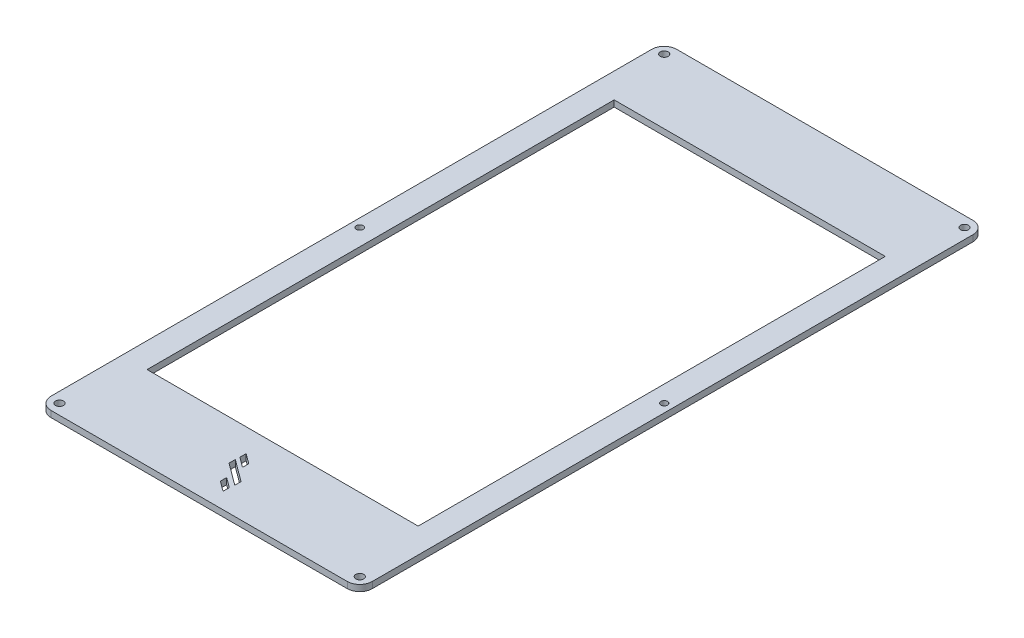
SolidWorks part; units mm, degrees
ref_plane "前视基准面" through (0, 0, 0) normal (0, 0, 1) x (1, 0, 0)
ref_plane "上视基准面" through (0, 0, 0) normal (0, 1, 0) x (1, 0, 0)
ref_plane "右视基准面" through (0, 0, 0) normal (1, 0, 0) x (0, 0, -1)
sketch "草图1" plane through (0.249, 0, -75.7072) normal (0, 1, 0) x (1, 0, 0)
  line L0 (-212.3169, 718.1207) -> (-234.7066, 815.582) construction
  line L1 (-132.5632, 1387.3532) -> (-132.5632, 1244.1403) construction
  line L2 (-45.1474, 1386.0064) -> (-45.1474, 1242.0064)
  line L3 (-110.6474, 1387.5064) -> (-86.8035, 1387.5064)
  line L4 (-120.6474, 1377.5064) -> (-120.6474, 1369.0064)
  line L5 (-110.6474, 1240.5064) -> (-86.8035, 1240.5064)
  line L6 (-46.6474, 1377.5064) -> (-46.6474, 1369.0064)
  line L7 (-119.1474, 1239.0064) -> (-48.1474, 1239.0064)
  line L8 (-122.1474, 1386.0064) -> (-122.1474, 1242.0064)
  line L9 (-119.1474, 1389.0064) -> (-48.1474, 1389.0064)
  line L10 (-120.6474, 1240.5064) -> (-46.6474, 1240.5064) construction
  line L11 (-46.6474, 1387.5064) -> (-46.6474, 1240.5064) construction
  line L12 (-120.6474, 1387.5064) -> (-120.6474, 1240.5064) construction
  line L13 (-120.6474, 1387.5064) -> (-46.6474, 1387.5064) construction
  line L14 (-45.1474, 1389.0064) -> (-45.1474, 1239.0064) construction
  line L15 (-122.1474, 1239.0064) -> (-45.1474, 1239.0064) construction
  line L16 (-122.1474, 1389.0064) -> (-122.1474, 1239.0064) construction
  line L17 (-122.1474, 1389.0064) -> (-45.1474, 1389.0064) construction
  line L18 (-83.6474, 1387.5064) -> (-83.6474, 1240.5064) construction
  line L19 (-46.6474, 1369.0064) -> (-49.0442, 1369.0064)
  line L21 (-46.6474, 1366.0064) -> (-49.0442, 1366.0064)
  line L22 (-49.0442, 1369.0064) -> (-49.0442, 1366.0064)
  line L23 (-46.6474, 1314.0064) -> (-120.6474, 1314.0064) construction
  line L24 (-46.6474, 1366.0064) -> (-46.6474, 1262.0064)
  line L25 (-46.6474, 1259.0064) -> (-49.0442, 1259.0064)
  line L26 (-49.0442, 1259.0064) -> (-49.0442, 1262.0064)
  line L27 (-46.6474, 1262.0064) -> (-49.0442, 1262.0064)
  line L28 (-120.6474, 1369.0064) -> (-118.2507, 1369.0064)
  line L29 (-118.2507, 1369.0064) -> (-118.2507, 1366.0064)
  line L30 (-120.6474, 1366.0064) -> (-118.2507, 1366.0064)
  line L31 (-120.6474, 1262.0064) -> (-118.2507, 1262.0064)
  line L32 (-118.2507, 1259.0064) -> (-118.2507, 1262.0064)
  line L33 (-46.6474, 1259.0064) -> (-46.6474, 1250.5064)
  line L34 (-120.6474, 1366.0064) -> (-120.6474, 1262.0064)
  line L35 (-118.2507, 1259.0064) -> (-120.6474, 1259.0064)
  line L36 (-120.6474, 1259.0064) -> (-120.6474, 1250.5064)
  line L37 (-79.37, 1387.5064) -> (-56.6474, 1387.5064)
  line L39 (-79.37, 1387.5064) -> (-79.37, 1384.5064)
  line L40 (-79.37, 1384.5064) -> (-86.8035, 1384.5064)
  line L41 (-86.8035, 1387.5064) -> (-86.8035, 1384.5064)
  line L43 (-80.7882, 1240.5064) -> (-80.7882, 1243.5064)
  line L44 (-80.7882, 1243.5064) -> (-86.8035, 1243.5064)
  line L45 (-86.8035, 1240.5064) -> (-86.8035, 1243.5064)
  line L46 (-80.7882, 1240.5064) -> (-56.6474, 1240.5064)
  arc A0 (-56.6474, 1240.5064) -> (-46.6474, 1250.5064) centre (-56.6474, 1250.5064) ccw
  arc A1 (-120.6474, 1250.5064) -> (-110.6474, 1240.5064) centre (-110.6474, 1250.5064) ccw
  arc A2 (-110.6474, 1387.5064) -> (-120.6474, 1377.5064) centre (-110.6474, 1377.5064) ccw
  arc A3 (-56.6474, 1387.5064) -> (-46.6474, 1377.5064) centre (-56.6474, 1377.5064) cw
  arc A4 (-45.1474, 1242.0064) -> (-48.1474, 1239.0064) centre (-48.1474, 1242.0064) cw
  arc A5 (-119.1474, 1239.0064) -> (-122.1474, 1242.0064) centre (-119.1474, 1242.0064) cw
  arc A6 (-122.1474, 1386.0064) -> (-119.1474, 1389.0064) centre (-119.1474, 1386.0064) cw
  arc A7 (-45.1474, 1386.0064) -> (-48.1474, 1389.0064) centre (-48.1474, 1386.0064) ccw
  point P48 (-47.8458, 1259.0064)
  point P55 (-119.4491, 1259.0064)
  dimension "D3" = 10
  dimension "D4" = 3
  dimension "D1" = 100
  dimension "D5" = 3
  dimension "D6" = 20
  dimension "D7" = 2.3967
  dimension "D8" = 71
  dimension "D9" = 144
  dimension "D10" = 3
  dimension "D11" = 3
  dimension "D2" = 1.5
extrude "凸台-拉伸1" add sketch "草图1" along normal blind 15
fillet "圆角1" radius 1 12 edges at (-118.0016, 7.5, -1334.7135) (-118.0016, 7.5, -1337.7135) (-48.7951, 7.5, -1334.7135) (-48.7951, 7.5, -1337.7135) (-48.7951, 7.5, -1441.7135) (-48.7951, 7.5, -1444.7135) (-118.0016, 7.5, -1441.7135) (-118.0016, 7.5, -1444.7135) (-86.5544, 7.5, -1319.2135) (-80.5392, 7.5, -1319.2135) (-79.1209, 7.5, -1460.2135) (-86.5544, 7.5, -1460.2135)
sketch "草图2" plane through (0.249, 15, -75.7072) normal (0, 1, 0) x (1, 0, 0)
  line L0 (-117.9843, 1353.593) -> (-118.8671, 1253.5969) construction
  line L1 (-65.1474, 1308.7566) -> (-65.1474, 1318.5064)
  line L2 (-66.1474, 1319.5064) -> (-92.1474, 1319.5064)
  line L3 (-93.1474, 1318.5064) -> (-93.1474, 1313.0064)
  line L4 (-45.1474, 1242.0064) -> (-45.1474, 1386.0064)
  line L5 (-48.1474, 1389.0064) -> (-119.1474, 1389.0064)
  line L6 (-122.1474, 1386.0064) -> (-122.1474, 1242.0064)
  line L7 (-119.1474, 1239.0064) -> (-48.1474, 1239.0064)
  line L8 (-45.1474, 1242.0064) -> (-45.1474, 1386.0064)
  line L9 (-48.1474, 1389.0064) -> (-119.1474, 1389.0064)
  line L10 (-122.1474, 1386.0064) -> (-122.1474, 1242.0064)
  line L11 (-119.1474, 1239.0064) -> (-48.1474, 1239.0064)
  line L12 (-94.1474, 1312.0064) -> (-95.1474, 1312.0064)
  line L13 (-96.1474, 1311.0064) -> (-96.1474, 1305.0064)
  line L14 (-95.1474, 1304.0064) -> (-86.1474, 1304.0064)
  line L15 (-85.1474, 1303.0064) -> (-85.1474, 1274.0064)
  line L16 (-84.1474, 1273.0064) -> (-65.1474, 1273.0064)
  line L17 (-89.1474, 1277.5064) -> (-99.1474, 1277.5064)
  line L18 (-100.1474, 1278.5064) -> (-100.1474, 1283.5064)
  line L19 (-99.1474, 1284.5064) -> (-89.1474, 1284.5064)
  line L20 (-88.1474, 1283.5064) -> (-88.1474, 1278.5064)
  line L21 (-84.6474, 1378.5064) -> (-84.6474, 1328.5064) construction
  line L22 (-104.1474, 1374.0064) -> (-65.1474, 1374.0064)
  line L23 (-105.1474, 1373.0064) -> (-105.1474, 1334.0064)
  line L24 (-104.1474, 1333.0064) -> (-65.1474, 1333.0064)
  line L25 (-64.1474, 1373.0064) -> (-64.1474, 1334.0064)
  line L26 (-65.1474, 1273.0064) -> (-64.1474, 1273.0064)
  line L27 (-65.1474, 1308.7566) -> (-55.8177, 1308.7566)
  line L28 (-64.1474, 1273.0064) -> (-64.1474, 1269.7566)
  line L29 (-63.1474, 1268.7566) -> (-56.8177, 1268.7566)
  line L30 (-55.8177, 1308.7566) -> (-55.8177, 1269.7566)
  arc A0 (-65.1474, 1318.5064) -> (-66.1474, 1319.5064) centre (-66.1474, 1318.5064) ccw
  arc A2 (-85.1474, 1274.0064) -> (-84.1474, 1273.0064) centre (-84.1474, 1274.0064) ccw
  arc A3 (-86.1474, 1304.0064) -> (-85.1474, 1303.0064) centre (-86.1474, 1303.0064) cw
  arc A4 (-48.1474, 1239.0064) -> (-45.1474, 1242.0064) centre (-48.1474, 1242.0064) ccw
  arc A5 (-45.1474, 1386.0064) -> (-48.1474, 1389.0064) centre (-48.1474, 1386.0064) ccw
  arc A6 (-119.1474, 1389.0064) -> (-122.1474, 1386.0064) centre (-119.1474, 1386.0064) ccw
  arc A7 (-122.1474, 1242.0064) -> (-119.1474, 1239.0064) centre (-119.1474, 1242.0064) ccw
  arc A8 (-48.1474, 1239.0064) -> (-45.1474, 1242.0064) centre (-48.1474, 1242.0064) ccw
  arc A9 (-45.1474, 1386.0064) -> (-48.1474, 1389.0064) centre (-48.1474, 1386.0064) ccw
  arc A10 (-119.1474, 1389.0064) -> (-122.1474, 1386.0064) centre (-119.1474, 1386.0064) ccw
  arc A11 (-122.1474, 1242.0064) -> (-119.1474, 1239.0064) centre (-119.1474, 1242.0064) ccw
  arc A12 (-92.1474, 1319.5064) -> (-93.1474, 1318.5064) centre (-92.1474, 1318.5064) ccw
  arc A13 (-93.1474, 1313.0064) -> (-94.1474, 1312.0064) centre (-94.1474, 1313.0064) cw
  arc A14 (-95.1474, 1312.0064) -> (-96.1474, 1311.0064) centre (-95.1474, 1311.0064) ccw
  arc A15 (-96.1474, 1305.0064) -> (-95.1474, 1304.0064) centre (-95.1474, 1305.0064) ccw
  arc A16 (-89.1474, 1284.5064) -> (-88.1474, 1283.5064) centre (-89.1474, 1283.5064) cw
  arc A17 (-89.1474, 1277.5064) -> (-88.1474, 1278.5064) centre (-89.1474, 1278.5064) ccw
  arc A18 (-99.1474, 1277.5064) -> (-100.1474, 1278.5064) centre (-99.1474, 1278.5064) cw
  arc A19 (-100.1474, 1283.5064) -> (-99.1474, 1284.5064) centre (-99.1474, 1283.5064) cw
  arc A20 (-65.1474, 1333.0064) -> (-64.1474, 1334.0064) centre (-65.1474, 1334.0064) ccw
  arc A21 (-105.1474, 1334.0064) -> (-104.1474, 1333.0064) centre (-104.1474, 1334.0064) ccw
  arc A22 (-104.1474, 1374.0064) -> (-105.1474, 1373.0064) centre (-104.1474, 1373.0064) ccw
  arc A23 (-65.1474, 1374.0064) -> (-64.1474, 1373.0064) centre (-65.1474, 1373.0064) cw
  circle A24 centre (-84.6474, 1378.5064) radius 1.5
  circle A25 centre (-84.6474, 1328.5064) radius 1.5
  arc A26 (-64.1474, 1269.7566) -> (-63.1474, 1268.7566) centre (-63.1474, 1269.7566) ccw
  arc A27 (-56.8177, 1268.7566) -> (-55.8177, 1269.7566) centre (-56.8177, 1269.7566) ccw
  point P28 (-65.1474, 1319.5064)
  point P31 (-65.1474, 1273.0064)
  point P34 (-85.1474, 1273.0064)
  point P37 (-85.1474, 1304.0064)
  point P40 (-93.1474, 1319.5064)
  point P43 (-93.1474, 1312.0064)
  point P46 (-96.1474, 1312.0064)
  point P49 (-96.1474, 1304.0064)
  point P52 (-88.1474, 1284.5064)
  point P55 (-88.1474, 1277.5064)
  point P58 (-100.1474, 1277.5064)
  point P69 (-105.1474, 1333.0064)
  point P72 (-105.1474, 1374.0064)
  point P75 (-64.1474, 1374.0064)
  point P78 (-84.6474, 1353.5064)
  point P79 (-64.1474, 1353.5064)
  dimension "D15" = 1
  dimension "D20" = 1
  dimension "D22" = 34
  dimension "D23" = 1
  dimension "D2" = 100
  dimension "D3" = 20
  dimension "D4" = 28
  dimension "D5" = 7.5
  dimension "D6" = 8
  dimension "D7" = 11
  dimension "D8" = 3
  dimension "D9" = 31
  dimension "D10" = 39
  dimension "D11" = 46.5
  dimension "D12" = 22
  dimension "D13" = 12
  dimension "D14" = 7
  dimension "D16" = 19
  dimension "D17" = 15
  dimension "D18" = 41
  dimension "D19" = 41
  dimension "D21" = 50
  dimension "D24" = 38.5
  dimension "D1" = 0
extrude "凸台-拉伸2" add sketch "草图2" against normal blind 2
fillet "圆角7" radius 1 3 edges at (-63.8984, 14, -1348.7135) (-55.5686, 14, -1384.4637) (-64.8984, 14, -1384.4637)
fillet "圆角2" radius 1 50 edges at (-78.8984, 15, -1395.2135) (-92.6055, 15, -1394.9206) (-92.8984, 15, -1391.4635) (-93.1913, 15, -1388.0064) (-94.3984, 15, -1387.7135) (-95.6055, 15, -1387.4206) (-95.8984, 15, -1383.7135) (-95.6055, 15, -1380.0064) (-90.3984, 15, -1379.7135) (-85.1913, 15, -1379.4206) (-84.8984, 15, -1364.2135) (-84.6055, 15, -1349.0064) (-74.3984, 15, -1348.7135) (-64.8984, 15, -1389.8386) (-65.1913, 15, -1394.9206) (-93.8984, 15, -1360.2135) (-99.6055, 15, -1359.9206) (-99.8984, 15, -1356.7135) (-99.6055, 15, -1353.5064) (-93.8984, 15, -1353.2135) (-88.1913, 15, -1353.5064) (-87.8984, 15, -1356.7135) (-88.1913, 15, -1359.9206) (-83.3984, 15, -1314.7135) (-121.0197, 15, -1315.5922) (-121.8984, 15, -1389.7135) (-121.0197, 15, -1463.8349) (-83.3984, 15, -1464.7135) (-45.7771, 15, -1463.8349) (-44.8984, 15, -1389.7135) (-45.7771, 15, -1315.5922) (-63.8984, 15, -1429.2135) (-64.1913, 15, -1449.4206) (-84.3984, 15, -1449.7135) (-104.6055, 15, -1449.4206) (-104.8984, 15, -1429.2135) (-104.6055, 15, -1409.0064) (-84.3984, 15, -1408.7135) (-64.1913, 15, -1409.0064) (-84.3984, 15, -1452.7135) (-84.3984, 15, -1402.7135) (-59.7335, 15, -1344.4637) (-55.8615, 15, -1344.7566) (-55.5686, 15, -1364.4637) (-60.2335, 15, -1384.4637) (-63.8984, 15, -1346.5886) (-63.6055, 15, -1344.7566) (-55.8615, 15, -1384.1708) (-64.6055, 15, -1384.7566) (-64.1913, 15, -1348.4206)
fillet "圆角3" radius 1 25 edges at (-48.5022, 0, -1337.4206) (-47.0968, 0, -1337.7135) (-48.7951, 0, -1336.2135) (-48.5022, 0, -1335.0064) (-47.0968, 0, -1334.7135) (-119.7, 0, -1337.7135) (-118.2945, 0, -1337.4206) (-118.0016, 0, -1336.2135) (-118.2945, 0, -1335.0064) (-119.7, 0, -1444.7135) (-118.2945, 0, -1444.4206) (-118.0016, 0, -1443.2135) (-118.2945, 0, -1442.0064) (-86.5544, 0, -1462.2135) (-86.2615, 0, -1460.5064) (-82.8377, 0, -1460.2135) (-79.4138, 0, -1460.5064) (-47.0968, 0, -1444.7135) (-48.5022, 0, -1444.4206) (-48.7951, 0, -1443.2135) (-48.5022, 0, -1442.0064) (-119.7, 0, -1334.7135) (-119.7, 0, -1441.7135) (-79.1209, 0, -1462.2135) (-47.0968, 0, -1441.7135)
fillet "圆角4" radius 1 86 edges at (-74.3984, 13, -1348.7135) (-84.6055, 13, -1349.0064) (-84.8984, 13, -1364.2135) (-85.1913, 13, -1379.4206) (-90.3984, 13, -1379.7135) (-95.6055, 13, -1380.0064) (-95.8984, 13, -1383.7135) (-95.6055, 13, -1387.4206) (-94.3984, 13, -1387.7135) (-93.1913, 13, -1388.0064) (-92.8984, 13, -1391.4635) (-92.6055, 13, -1394.9206) (-78.8984, 13, -1395.2135) (-65.1913, 13, -1394.9206) (-64.8984, 13, -1389.8386) (-88.1913, 13, -1353.5064) (-93.8984, 13, -1353.2135) (-99.6055, 13, -1353.5064) (-99.8984, 13, -1356.7135) (-99.6055, 13, -1359.9206) (-93.8984, 13, -1360.2135) (-88.1913, 13, -1359.9206) (-87.8984, 13, -1356.7135) (-86.2615, 13, -1318.9206) (-83.5468, 13, -1319.2135) (-80.8321, 13, -1318.9206) (-80.5392, 13, -1317.2135) (-68.4688, 13, -1316.2135) (-49.3273, 13, -1319.1425) (-46.3984, 13, -1330.4635) (-47.0968, 13, -1334.7135) (-48.5022, 13, -1335.0064) (-48.7951, 13, -1336.2135) (-48.5022, 13, -1337.4206) (-47.0968, 13, -1337.7135) (-46.3984, 13, -1389.7135) (-47.0968, 13, -1441.7135) (-48.5022, 13, -1442.0064) (-48.7951, 13, -1443.2135) (-48.5022, 13, -1444.4206) (-47.0968, 13, -1444.7135) (-46.3984, 13, -1448.9635) (-49.3273, 13, -1460.2846) (-67.7597, 13, -1463.2135) (-79.1209, 13, -1462.2135) (-79.4138, 13, -1460.5064) (-82.8377, 13, -1460.2135) (-86.2615, 13, -1460.5064) (-86.5544, 13, -1462.2135) (-98.4764, 13, -1463.2135) (-117.4695, 13, -1460.2846) (-120.3984, 13, -1448.9635) (-119.7, 13, -1444.7135) (-118.2945, 13, -1444.4206) (-118.0016, 13, -1443.2135) (-118.2945, 13, -1442.0064) (-119.7, 13, -1441.7135) (-120.3984, 13, -1389.7135) (-119.7, 13, -1337.7135) (-118.2945, 13, -1337.4206) (-118.0016, 13, -1336.2135) (-118.2945, 13, -1335.0064) (-119.7, 13, -1334.7135) (-120.3984, 13, -1330.4635) (-117.4695, 13, -1319.1425) (-98.4764, 13, -1316.2135) (-86.5544, 13, -1317.2135) (-104.6055, 13, -1409.0064) (-104.8984, 13, -1429.2135) (-104.6055, 13, -1449.4206) (-84.3984, 13, -1449.7135) (-64.1913, 13, -1449.4206) (-63.8984, 13, -1429.2135) (-64.1913, 13, -1409.0064) (-84.3984, 13, -1408.7135) (-84.3984, 13, -1452.7135) (-84.3984, 13, -1402.7135) (-60.2335, 13, -1384.4637) (-55.5686, 13, -1364.4637) (-55.8615, 13, -1344.7566) (-59.7335, 13, -1344.4637) (-63.6055, 13, -1344.7566) (-63.8984, 13, -1346.5886) (-64.6055, 13, -1384.7566) (-55.8615, 13, -1384.1708) (-64.1913, 13, -1348.4206)
sketch "草图3" plane through (0.249, 0, -75.7072) normal (0, -1, 0) x (1, 0, 0)
  line L0 (-119.1474, -1239.0064) -> (-48.1474, -1239.0064) construction
  line L2 (-45.1474, -1242.0064) -> (-45.1474, -1386.0064) construction
  line L3 (-45.1474, -1314.0064) -> (-122.1474, -1314.0064) construction
  line L4 (-122.1474, -1386.0064) -> (-122.1474, -1242.0064) construction
  line L5 (-83.6474, -1314.0064) -> (-83.6474, -1389.0064) construction
  line L6 (-48.1474, -1389.0064) -> (-119.1474, -1389.0064) construction
  circle A0 centre (-47.6474, -1241.5064) radius 0.95
  circle A1 centre (-47.6474, -1386.5064) radius 0.95
  circle A2 centre (-119.6474, -1386.5064) radius 0.95
  circle A3 centre (-119.6474, -1241.5064) radius 0.95
  dimension "D2" = 1.9
  dimension "D3" = 2.5
  dimension "D1" = 2.5
extrude "切除-拉伸1" cut sketch "草图3" against normal blind 10
sketch "草图4" plane through (0.249, 13, -75.7072) normal (0, -1, 0) x (1, 0, 0)
  line L7 (-92.1474, -1320.5064) -> (-66.0382, -1320.5064)
  line L8 (-92.1474, -1320.5064) -> (-92.1474, -1323.5064)
  line L9 (-91.1474, -1324.5064) -> (-67.0382, -1324.5064)
  line L10 (-66.0382, -1320.5064) -> (-66.0382, -1323.5064)
  arc A4 (-92.1474, -1323.5064) -> (-91.1474, -1324.5064) centre (-91.1474, -1323.5064) ccw
  arc A5 (-67.0382, -1324.5064) -> (-66.0382, -1323.5064) centre (-67.0382, -1323.5064) ccw
  point P28 (-66.0382, -1324.5064)
  dimension "D7" = 1
  dimension "D6" = 4
extrude "凸台-拉伸3" add sketch "草图4" along normal blind 3
fillet "圆角6" radius 1 6 edges at (-78.8438, 10, -1396.2135) (-65.7892, 10, -1397.7135) (-66.0821, 10, -1399.9206) (-78.8438, 10, -1400.2135) (-91.6055, 10, -1399.9206) (-91.8984, 10, -1397.7135)
sketch "草图5" plane through (0.249, 15, -75.7072) normal (0, 1, 0) x (1, 0, 0)
  line L0 (-53.1474, 1307.5064) -> (-53.1474, 1332.5064) construction
  line L1 (-45.1474, 1386.0064) -> (-45.1474, 1242.0064) construction
  line L2 (-53.1474, 1320.0064) -> (-58.1474, 1320.0064) construction
  line L3 (-83.6474, 1240.0064) -> (-83.6474, 1388.0064) construction
  line L4 (-119.1474, 1240.0064) -> (-48.1474, 1240.0064) construction
  line L5 (-48.1474, 1388.0064) -> (-119.1474, 1388.0064) construction
  line L6 (-114.1474, 1320.0064) -> (-109.1474, 1320.0064) construction
  line L7 (-114.1474, 1307.5064) -> (-114.1474, 1332.5064) construction
  circle A0 centre (-58.1474, 1320.0064) radius 1
  circle A1 centre (-53.1474, 1307.5064) radius 1
  circle A2 centre (-53.1474, 1332.5064) radius 1
  circle A3 centre (-114.1474, 1332.5064) radius 1
  circle A4 centre (-114.1474, 1307.5064) radius 1
  circle A5 centre (-109.1474, 1320.0064) radius 1
  dimension "D4" = 80
  dimension "D1" = 8
  dimension "D2" = 25
  dimension "D3" = 5
extrude "切除-拉伸2" cut sketch "草图5" against normal up to surface (2 mm away) up to face at (-83.3422, 13, -1389.7135)
sketch "草图6" plane through (0, 0, 0) normal (0, -1, 0) x (1, 0, 0)
  line L4 (-47.8984, -1314.7135) -> (-118.8984, -1314.7135)
  line L5 (-121.8984, -1317.7135) -> (-121.8984, -1461.7135)
  line L6 (-118.8984, -1464.7135) -> (-47.8984, -1464.7135)
  line L7 (-44.8984, -1461.7135) -> (-44.8984, -1317.7135)
  line L8 (-47.8984, -1314.7135) -> (-118.8984, -1314.7135)
  line L9 (-121.8984, -1317.7135) -> (-121.8984, -1461.7135)
  line L10 (-118.8984, -1464.7135) -> (-47.8984, -1464.7135)
  line L11 (-44.8984, -1461.7135) -> (-44.8984, -1317.7135)
  circle A0 centre (-119.3984, -1462.2135) radius 0.95 construction
  circle A1 centre (-119.3984, -1317.2135) radius 0.95 construction
  circle A2 centre (-47.3984, -1462.2135) radius 0.95 construction
  circle A3 centre (-47.3984, -1317.2135) radius 0.95 construction
  arc A4 (-44.8984, -1317.7135) -> (-47.8984, -1314.7135) centre (-47.8984, -1317.7135) ccw
  arc A5 (-118.8984, -1314.7135) -> (-121.8984, -1317.7135) centre (-118.8984, -1317.7135) ccw
  arc A6 (-121.8984, -1461.7135) -> (-118.8984, -1464.7135) centre (-118.8984, -1461.7135) ccw
  arc A7 (-47.8984, -1464.7135) -> (-44.8984, -1461.7135) centre (-47.8984, -1461.7135) ccw
  arc A8 (-44.8984, -1317.7135) -> (-47.8984, -1314.7135) centre (-47.8984, -1317.7135) ccw
  arc A9 (-118.8984, -1314.7135) -> (-121.8984, -1317.7135) centre (-118.8984, -1317.7135) ccw
  arc A10 (-121.8984, -1461.7135) -> (-118.8984, -1464.7135) centre (-118.8984, -1461.7135) ccw
  arc A11 (-47.8984, -1464.7135) -> (-44.8984, -1461.7135) centre (-47.8984, -1461.7135) ccw
  circle A12 centre (-119.3984, -1462.2135) radius 0.95
  circle A13 centre (-119.3984, -1317.2135) radius 0.95
  circle A14 centre (-47.3984, -1462.2135) radius 0.95
  circle A15 centre (-47.3984, -1317.2135) radius 0.95
  dimension "D1" = 0
extrude "凸台-拉伸4" add sketch "草图6" along normal blind 1.5
sketch "草图7" plane through (0, 15, 0) normal (0, 1, 0) x (1, 0, 0)
  line L1 (-40.7857, 1471.5473) -> (-132.3564, 1471.5473)
  line L2 (-40.7857, 1471.5473) -> (-40.7857, 1303.1754)
  line L3 (-40.7857, 1303.1754) -> (-132.3564, 1303.1754)
  line L4 (-132.3564, 1471.5473) -> (-132.3564, 1303.1754)
extrude "切除-拉伸3" cut sketch "草图7" against normal offset from surface (15 mm away) 1.5 up to face at (-47.3984, -1.5, -1463.1635)
sketch "草图8" plane through (0, -1.5, 0) normal (0, -1, 0) x (1, 0, 0)
  line L0 (-47.8984, -1314.7135) -> (-118.8984, -1314.7135) construction
  line L1 (-50.8984, -1332.7135) -> (-115.8984, -1332.7135)
  line L2 (-50.8984, -1332.7135) -> (-50.8984, -1448.7135)
  line L3 (-50.8984, -1448.7135) -> (-115.8984, -1448.7135)
  line L4 (-115.8984, -1332.7135) -> (-115.8984, -1448.7135)
  line L5 (-118.8984, -1464.7135) -> (-47.8984, -1464.7135) construction
  line L6 (-121.8984, -1317.7135) -> (-121.8984, -1461.7135) construction
  line L7 (-44.8984, -1461.7135) -> (-44.8984, -1317.7135) construction
  dimension "D1" = 18
  dimension "D2" = 16
  dimension "D3" = 6
  dimension "D4" = 6
extrude "切除-拉伸4" cut sketch "草图8" against normal up to surface (1.5 mm away) contours L1 L4 L3 L2 up to face at (-119.3984, 0, -1463.1635)
sketch "草图9" plane through (0, -1.5, 0) normal (0, -1, 0) x (1, 0, 0)
  line L0 (-81.3638, -1321.2082) -> (-81.3638, -1322.7095)
  line L1 (-81.3638, -1321.2082) -> (-86.6379, -1325.1082)
  line L2 (-81.3638, -1322.7095) -> (-86.6379, -1326.6095)
  line L3 (-86.6379, -1325.1082) -> (-86.6379, -1326.6095)
  line L4 (-81.5204, -1318.5475) -> (-81.5204, -1320.0488)
  line L5 (-81.5204, -1318.5475) -> (-83.9379, -1320.3351)
  line L6 (-81.5204, -1320.0488) -> (-83.9379, -1321.8364)
  line L7 (-83.9379, -1320.3351) -> (-83.9379, -1321.8364)
  line L8 (-84.1533, -1325.8526) -> (-84.1533, -1327.354)
  line L9 (-84.1533, -1325.8526) -> (-86.5707, -1327.6402)
  line L10 (-84.1533, -1327.354) -> (-86.5707, -1329.1416)
  line L11 (-86.5707, -1327.6402) -> (-86.5707, -1329.1416)
extrude "切除-拉伸5" cut sketch "草图9" against normal blind 1.5
sketch "草图10" plane through (0, -1.5, 0) normal (0, -1, 0) x (1, 0, 0)
  line L1 (-50.8984, -1334.7135) -> (-115.8984, -1334.7135)
  line L3 (-50.8984, -1446.7135) -> (-115.8984, -1446.7135)
  line L6 (-50.8984, -1332.7135) -> (-115.8984, -1332.7135) construction
  line L7 (-50.8984, -1448.7135) -> (-115.8984, -1448.7135) construction
  line L8 (-50.8984, -1334.7135) -> (-50.8984, -1332.7135)
  line L9 (-50.8984, -1332.7135) -> (-115.8984, -1332.7135)
  line L10 (-115.8984, -1332.7135) -> (-115.8984, -1334.7135)
  line L11 (-50.8984, -1446.7135) -> (-50.8984, -1448.7135)
  line L12 (-50.8984, -1448.7135) -> (-115.8984, -1448.7135)
  line L13 (-115.8984, -1448.7135) -> (-115.8984, -1446.7135)
  dimension "D1" = 2
  dimension "D2" = 2
extrude "凸台-拉伸5" add sketch "草图10" against normal up to surface (1.5 mm away) up to face at (-84.0008, 0, -1323.9089)
sketch "草图11" plane through (0, -1.5, 0) normal (0, -1, 0) x (1, 0, 0)
  line L0 (-44.8984, -1389.7135) -> (-46.8984, -1389.7135) construction
  line L1 (-44.8984, -1461.7135) -> (-44.8984, -1317.7135) construction
  line L2 (-83.3984, -1314.7135) -> (-83.3984, -1464.7135) construction
  line L3 (-47.8984, -1314.7135) -> (-118.8984, -1314.7135) construction
  line L4 (-118.8984, -1464.7135) -> (-47.8984, -1464.7135) construction
  circle A0 centre (-46.8984, -1389.7135) radius 0.8
  circle A1 centre (-119.8984, -1389.7135) radius 0.8
  dimension "D2" = 1.6
  dimension "D1" = 2
extrude "切除-拉伸6" cut sketch "草图11" against normal up to surface (1.5 mm away) up to face at (-83.3984, 0, -1390.7135)
